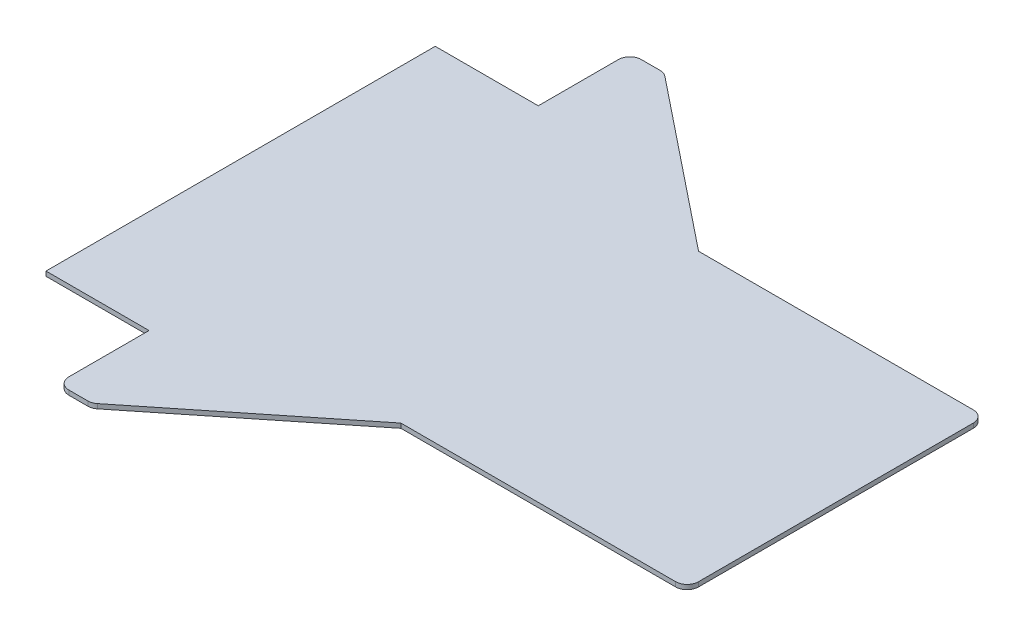
SolidWorks part; units mm, degrees
ref_plane "정면" through (0, 0, 0) normal (0, 0, 1) x (1, 0, 0)
ref_plane "윗면" through (0, 0, 0) normal (0, 1, 0) x (1, 0, 0)
ref_plane "우측면" through (0, 0, 0) normal (1, 0, 0) x (0, 0, -1)
sketch "스케치1" plane through (0, 0, 0) normal (0, 1, 0) x (1, 0, 0)
  line L1 (-130, -125) -> (130, -125)
  line L2 (-130, -125) -> (-130, 125)
  line L3 (-130, 125) -> (130, 125)
  line L4 (130, -125) -> (130, 125)
  line L5 (-130, -125) -> (130, 125) construction
  line L6 (-130, 125) -> (130, -125) construction
  point P0 (0, 0)
  dimension "D1" = 250
  dimension "D2" = 260
extrude "보스-돌출1" add sketch "스케치1" along normal blind 2
sketch "스케치2" plane through (0, 2, 0) normal (0, 1, 0) x (1, 0, 0)
  line L1 (130, 125) -> (5, 125)
  line L2 (130, 125) -> (130, 65)
  line L3 (130, 65) -> (5, 65)
  line L4 (5, 125) -> (5, 65)
  line L5 (130, -125) -> (5, -125)
  line L6 (130, -125) -> (130, -65)
  line L7 (130, -65) -> (5, -65)
  line L8 (5, -125) -> (5, -65)
  line L9 (-130, 125) -> (-85, 125)
  line L10 (-130, 125) -> (-130, 85)
  line L11 (-130, 85) -> (-85, 85)
  line L12 (-85, 125) -> (-85, 85)
  line L13 (-130, -125) -> (-85, -125)
  line L14 (-130, -125) -> (-130, -85)
  line L15 (-130, -85) -> (-85, -85)
  line L16 (-85, -125) -> (-85, -85)
  dimension "D1" = 125
  dimension "D2" = 60
  dimension "D3" = 40
  dimension "D4" = 90
extrude "컷-돌출1" cut sketch "스케치2" against normal blind 10
sketch "스케치3" plane through (0, 2, 0) normal (0, 1, 0) x (1, 0, 0)
  line L0 (-70, 125) -> (5, 65)
  line L1 (-70, -125) -> (5, -65)
  line L2 (5, -65) -> (5, -125)
  line L3 (5, -125) -> (-70, -125)
  line L4 (5, 65) -> (5, 125)
  line L5 (5, 125) -> (-70, 125)
  dimension "D1" = 75
extrude "컷-돌출2" cut sketch "스케치3" against normal blind 10
fillet "필렛1" radius 5 6 edges at (-70, 1, 125) (-70, 1, -125) (-85, 1, -125) (-85, 1, 125) (130, 1, 65) (130, 1, -65)
